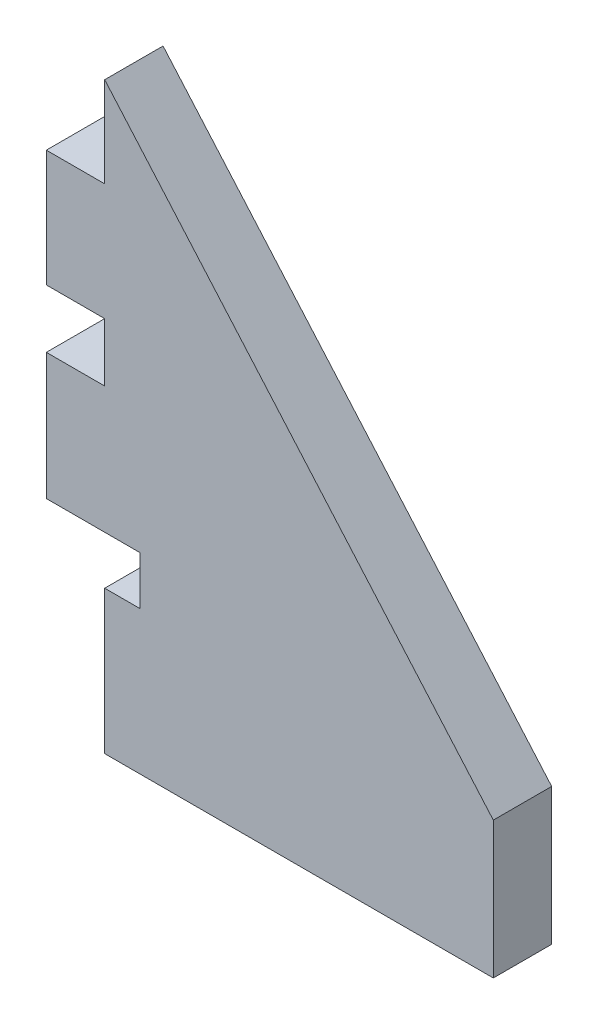
SolidWorks part; units mm, degrees
ref_plane "Front Plane" through (0, 0, 0) normal (0, 0, 1) x (1, 0, 0)
ref_plane "Top Plane" through (0, 0, 0) normal (0, 1, 0) x (1, 0, 0)
ref_plane "Right Plane" through (0, 0, 0) normal (1, 0, 0) x (0, 0, -1)
sketch "Sketch1" plane through (0, 0, 0) normal (0, 0, 1) x (1, 0, 0)
  line L0 (-12.3467, 38.1) -> (-18.6967, 38.1)
  line L1 (-18.6967, 38.1) -> (-18.6967, 25.4)
  line L2 (-18.6967, 25.4) -> (-12.3467, 25.4)
  line L3 (-12.3467, 25.4) -> (-12.3467, 19.05)
  line L4 (-12.3467, 19.05) -> (-18.6967, 19.05)
  line L5 (-18.6967, 19.05) -> (-18.6967, 5.2705)
  line L6 (-18.6967, 5.2705) -> (-12.3467, 5.2705)
  line L7 (-12.3467, 5.2705) -> (-8.5226, 5.2705)
  line L8 (-8.5226, 5.2705) -> (-8.5226, 0)
  line L9 (-5.7109, 0) -> (-12.3467, 0) construction
  line L10 (-8.5226, 0) -> (-12.3467, 0)
  line L11 (-12.3467, 0) -> (-12.3467, -15.5875)
  line L12 (-12.3467, -15.5875) -> (29.9353, -15.5875)
  line L13 (177.2366, -15.5875) -> (-12.3467, -15.5875) construction
  line L14 (29.9353, -15.5875) -> (29.9353, -0.7105)
  line L15 (29.9353, -0.7105) -> (-12.3467, 47.9125)
  line L16 (-12.3467, 47.9125) -> (-12.3467, 38.1)
extrude "Boss-Extrude1" add sketch "Sketch1" along normal blind 6.35
